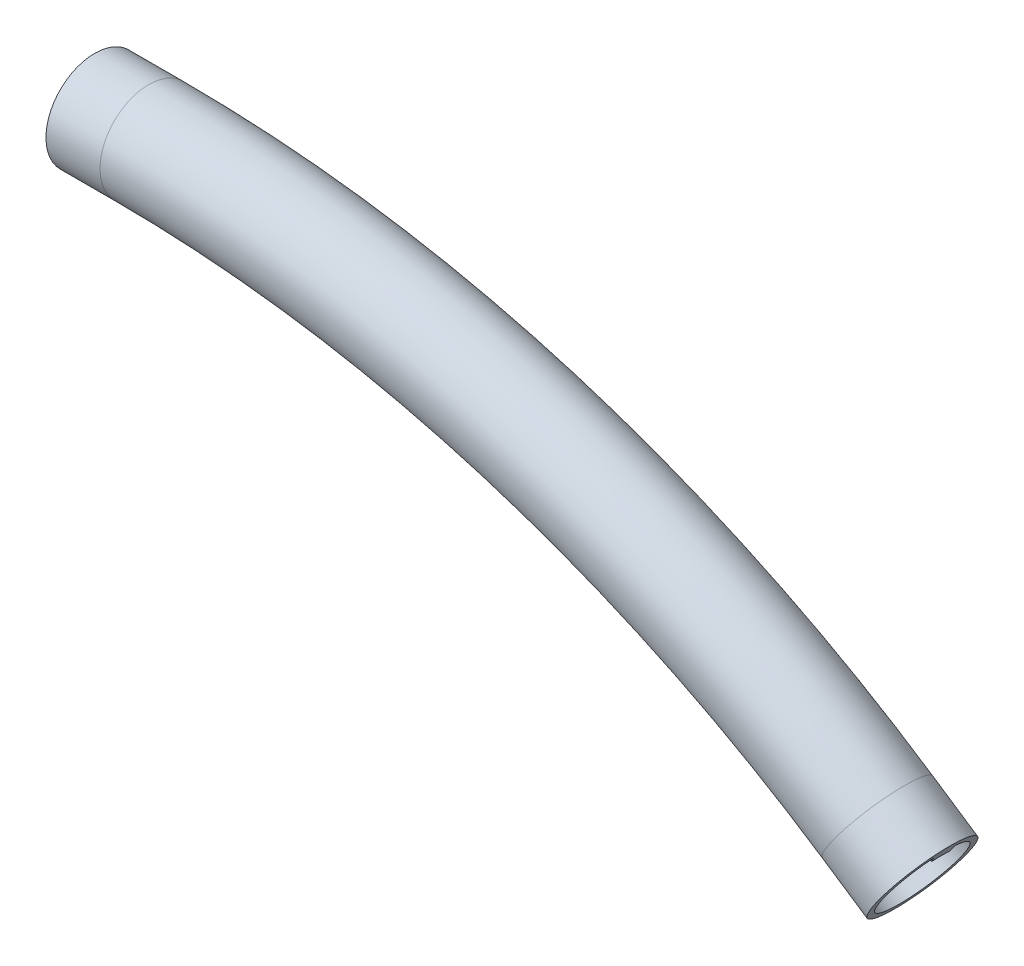
SolidWorks part; units mm, degrees
ref_plane "Front" through (0, 0, 0) normal (0, 0, 1) x (1, 0, 0)
ref_plane "Top" through (0, 0, 0) normal (0, 1, 0) x (1, 0, 0)
ref_plane "Right" through (0, 0, 0) normal (1, 0, 0) x (0, 0, -1)
sketch "Sketch2path" plane through (0, 0, 0) normal (0, 0, 1) x (1, 0, 0)
  line L2 (0, 100) -> (10, 100)
  line L3 (144.7958, 59.1102) -> (153.1105, 53.5545)
  arc A1 (10, 100) -> (144.7958, 59.1102) centre (10, -142.626) cw
  dimension "D1" = 160
  dimension "D3" = 10
  dimension "D4" = 10
  dimension "D5" = 33.75
sketch "Sketch3" plane through (0, 0, 0) normal (1, 0, 0) x (0, 0, -1)
  circle A0 centre (0, 100) radius 9
  circle A1 centre (0, 100) radius 7.75
  dimension "D1" = 1.25
  dimension "D2" = 18
  dimension "D3" = 100
sweep "Sweep1" add profiles "Sketch3" path "Sketch2path"
ref_point "Point1"
ref_point "Point2"
ref_axis "Axis1" through (153.1105, 53.5545, 0) along (0, 0, 1)
ref_axis "Axis2" through (0, 100, 0) along (0, 0, 1)
ref_axis "Axis3" through (10, 100, 0) along (-1, 0, 0)
ref_axis "Axis4" through (147.3622, 57.3953, 0) along (0.8315, -0.5556, 0)
ref_plane "Plane1" through (76.9554, -51.4199, 0) normal (0.8315, -0.5556, 0) x (0, 0, -1)
sketch "Sketch4" plane through (76.9554, -51.4199, 0) normal (0.8315, -0.5556, 0) x (0, 0, -1)
  line L1 (4.7631, 126.8425) -> (5.6292, 126.3425)
  line L3 (6.5, 129.5925) -> (5.5, 129.5925)
  arc A0 (5.6292, 126.3425) -> (6.5, 129.5925) centre (0, 129.5925) ccw
  arc A1 (4.7631, 126.8425) -> (5.5, 129.5925) centre (0, 129.5925) ccw
  dimension "D3" = 4.7631
  dimension "D4" = 126.3425
  dimension "D1" = 6.5
  dimension "D2" = 5.5
extrude "Boss-Extrude1" [suppressed] add sketch "Sketch4" against normal blind 5
ref_plane "Plane2" through (5, 0, 0) normal (-1, 0, 0) x (0, 0, 1)
sketch "Sketch5" plane through (5, 0, 0) normal (-1, 0, 0) x (0, 0, 1)
  line L0 (0, 100) -> (8.3914, 100) construction
  line L1 (-4.7631, 102.75) -> (-5.6292, 103.25)
  line L3 (-6.5, 100) -> (-5.5, 100)
  arc A0 (-5.6292, 103.25) -> (-6.5, 100) centre (0, 100) ccw
  arc A1 (-4.7631, 102.75) -> (-5.5, 100) centre (0, 100) ccw
  circle A3 centre (0, 100) radius 7.75 construction
  dimension "D3" = 1
  dimension "D1" = 30
  dimension "D2" = 6.5
extrude "Boss-Extrude2" [suppressed] add sketch "Sketch5" against normal blind 5
ref_plane "Plane3" [suppressed] through (0, 0, 9) normal (0, 0, 1) x (1, 0, 0)
sketch "Sketch6" [suppressed] plane through (0, 0, 9) normal (0, 0, 1) x (1, 0, 0)
  line L0 (0, 100) -> (0, 99.5)
  line L1 (0, 109) -> (0, 91) construction
  line L2 (0, 99.5) -> (3, 99.5)
  line L3 (3, 99.5) -> (3, 100)
  line L4 (10, 100) -> (-12.0198, 100) construction
  line L5 (3, 100) -> (0, 100)
  dimension "D1" = 0.5
  dimension "D2" = 3
revolve "Cut-Revolve1" [suppressed] cut sketch "Sketch6" angle 360 about L5
sketch "Sketch7" [suppressed] plane through (0, 0, 9) normal (0, 0, 1) x (1, 0, 0)
  line L0 (153.1105, 53.5545) -> (150.616, 55.2212)
  line L1 (148.1103, 46.0712) -> (158.1106, 61.0377) construction
  line L2 (147.3622, 57.3953) -> (165.8801, 45.0221) construction
  line L3 (150.616, 55.2212) -> (150.3383, 54.8054)
  line L4 (150.3383, 54.8054) -> (152.8327, 53.1387)
  line L5 (152.8327, 53.1387) -> (153.1105, 53.5545)
  dimension "D1" = 0.5
  dimension "D2" = 3
revolve "Cut-Revolve2" [suppressed] cut sketch "Sketch7" angle 360 about L0
sketch "Sketch8" plane through (81.1127, -54.1978, 0) normal (0.8315, -0.5556, 0) x (0, 0, -1)
  line L0 (-1.6176, 135.6295) -> (-2.0058, 137.0784)
  line L2 (2.0058, 137.0784) -> (1.6176, 135.6295)
  line L3 (-1.6676, 135.4081) -> (-2.0811, 136.85) construction
  arc A0 (2.0058, 137.0784) -> (-2.0058, 137.0784) centre (0, 129.5925) ccw
  arc A1 (1.6176, 135.6295) -> (-1.6176, 135.6295) centre (0, 129.5925) ccw
  circle A2 centre (0, 129.5925) radius 7.75 construction
  dimension "D3" = 1.5
  dimension "D1" = 30
  dimension "D2" = 1
extrude "Boss-Extrude3" add sketch "Sketch8" against normal blind 5
sketch "Sketch9" plane through (0, 0, 0) normal (-1, 0, 0) x (0, 0, 1)
  line L0 (-1.6176, 106.037) -> (-2.0058, 107.4859)
  line L2 (2.0058, 107.4859) -> (1.6176, 106.037)
  line L3 (2.0811, 107.2575) -> (1.6676, 105.8156) construction
  arc A0 (2.0058, 107.4859) -> (-2.0058, 107.4859) centre (0, 100) ccw
  arc A1 (1.6176, 106.037) -> (-1.6176, 106.037) centre (0, 100) ccw
  circle A2 centre (0, 100) radius 7.75 construction
  dimension "D1" = 1.5
  dimension "D2" = 30
  dimension "D3" = 1
extrude "Boss-Extrude4" add sketch "Sketch9" against normal blind 5 contours A1 L0 A0 L2
